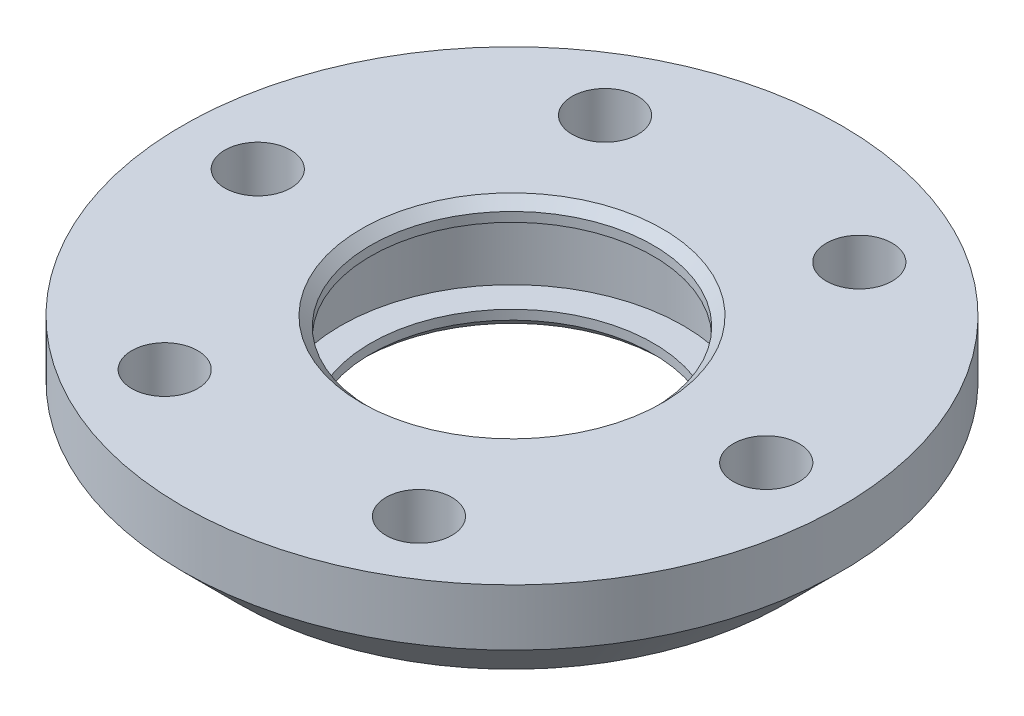
SolidWorks part; units mm, degrees
ref_plane "Front Plane" through (0, 0, 0) normal (0, 0, 1) x (1, 0, 0)
ref_plane "Top Plane" through (0, 0, 0) normal (0, 1, 0) x (1, 0, 0)
ref_plane "Right Plane" through (0, 0, 0) normal (1, 0, 0) x (0, 0, -1)
sketch "Sketch1" plane through (0, 0, 0) normal (0, 1, 0) x (1, 0, 0)
  circle A0 centre (0, 0) radius 13.5 construction
  circle A1 centre (13.5, 0) radius 1.75
  circle A2 centre (6.75, -11.6913) radius 1.75
  circle A3 centre (-6.75, -11.6913) radius 1.75
  circle A4 centre (-13.5, 0) radius 1.75
  circle A5 centre (-6.75, 11.6913) radius 1.75
  circle A6 centre (6.75, 11.6913) radius 1.75
  circle A7 centre (0, 0) radius 17.5
  circle A8 centre (0, 0) radius 7.5
  point P17 (0, 0)
  dimension "D1" = 27
  dimension "D2" = 3.5
  dimension "D4" = 35
  dimension "D5" = 15
  dimension "D3" = 6
extrude "Boss-Extrude1" add sketch "Sketch1" along normal mid plane 6
sketch "Sketch2" plane through (0, 0, 0) normal (0, 1, 0) x (1, 0, 0)
  circle A0 centre (0, 0) radius 9.1
  dimension "D1" = 18.2
extrude "Cut-Extrude1" cut sketch "Sketch2" against normal mid plane 4
sketch "Sketch3" plane through (0, -3, 0) normal (0, -1, 0) x (1, 0, 0)
  circle A0 centre (0, 0) radius 11.75
  circle A1 centre (0, 0) radius 15.25
  circle A2 centre (-13.5, 0) radius 1.75 construction
extrude "Boss-Extrude2" add sketch "Sketch3" against normal blind 1.5
chamfer "Chamfer1" distance 0.5 angle 45 2 edges at (0, -3, 7.5) (0, 3, 7.5)
sketch "Sketch4" [suppressed] plane through (0, 4.5, 0) normal (0, 1, 0) x (1, 0, 0)
  circle A0 centre (0, 0) radius 18.5
  circle A1 centre (0, 0) radius 17.5 construction
  circle A2 centre (0, 0) radius 17.5
  dimension "D1" = 1
extrude "Boss-Extrude3" [suppressed] add sketch "Sketch4" against normal blind 2
sketch "Sketch5" [suppressed] plane through (0, -4.5, 0) normal (0, -1, 0) x (-1, 0, 0)
  line L0 (0, 0) -> (-10.8253, -6.25) construction
  line L1 (0, 0) -> (-12.5, 0) construction
  circle A0 centre (0, 0) radius 12.5 construction
  circle A1 centre (-10.8253, -6.25) radius 2.35
  circle A2 centre (-10.8253, 6.25) radius 2.35
  circle A3 centre (0, 12.5) radius 2.35
  circle A4 centre (10.8253, 6.25) radius 2.35
  circle A5 centre (10.8253, -6.25) radius 2.35
  circle A6 centre (0, -12.5) radius 2.35
  point P18 (0, 0)
  dimension "D1" = 4.7
  dimension "D2" = 25
  dimension "D3" = 30
  dimension "D4" = 6
extrude "Cut-Extrude2" [suppressed] cut sketch "Sketch5" against normal blind 4
chamfer "Chamfer2" distance 3 angle 45 1 edges at (0, -3, 17.5)
equation "\"D5@Sketch1\"=18-3"
